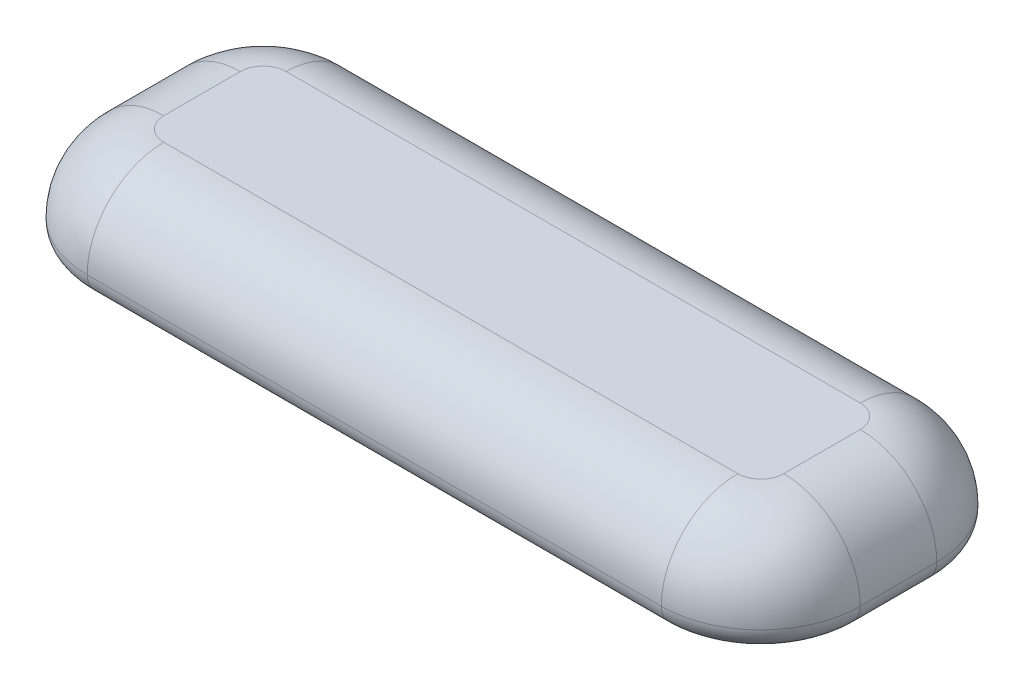
SolidWorks part; units mm, degrees
ref_plane "前视基准面" through (0, 0, 0) normal (0, 0, 1) x (1, 0, 0)
ref_plane "上视基准面" through (0, 0, 0) normal (0, 1, 0) x (1, 0, 0)
ref_plane "右视基准面" through (0, 0, 0) normal (1, 0, 0) x (0, 0, -1)
sketch "草图1" plane through (0, 0, 0) normal (0, 1, 0) x (1, 0, 0)
  line L1 (-37.5, 15) -> (37.5, 15)
  line L2 (-47.5, 5) -> (-47.5, -5)
  line L3 (-37.5, -15) -> (37.5, -15)
  line L4 (47.5, 5) -> (47.5, -5)
  line L5 (0, -15) -> (0, 15) construction
  line L6 (-47.5, 0) -> (47.5, 0) construction
  arc A0 (-47.5, -5) -> (-37.5, -15) centre (-37.5, -5) ccw
  arc A1 (-47.5, 5) -> (-37.5, 15) centre (-37.5, 5) cw
  arc A2 (37.5, 15) -> (47.5, 5) centre (37.5, 5) cw
  arc A3 (47.5, -5) -> (37.5, -15) centre (37.5, -5) cw
  point P0 (0, 0)
  point P8 (-47.5, 15)
  point P11 (47.5, 15)
  point P15 (47.5, -15)
  dimension "D3" = 10
  dimension "D1" = 95
  dimension "D2" = 30
extrude "凸台-拉伸1" add sketch "草图1" along normal blind 10
shell "抽壳2" thickness 3 removed face at (0, 0, 0) outward yes
fillet "圆角3" radius 10 8 edges at (46.6924, 13, -14.1924) (50.5, 13, 0) (46.6924, 13, 14.1924) (0, 13, 18) (-46.6924, 13, 14.1924) (-50.5, 13, 0) (-46.6924, 13, -14.1924) (0, 13, -18)
fillet "圆角4" radius 3 8 edges at (50.5, 0, 0) (46.6924, 0, 14.1924) (0, 0, 18) (-46.6924, 0, 14.1924) (-50.5, 0, 0) (-46.6924, 0, -14.1924) (0, 0, -18) (46.6924, 0, -14.1924)
ref_plane "基准面1" through (0, 10, 0) normal (0, -1, 0) x (-1, 0, 0)
sketch "草图2" plane through (0, 10, 0) normal (0, -1, 0) x (-1, 0, 0)
  line L0 (0, 0) -> (36.8, 0) construction
  line L1 (0, 0) -> (0, 6.5357) construction
  line L2 (34.725, 0.575) -> (38.875, 0.575)
  line L3 (34.725, 0.575) -> (34.725, -0.575)
  line L4 (34.725, -0.575) -> (38.875, -0.575)
  line L5 (38.875, 0.575) -> (38.875, -0.575)
  line L6 (36.8, -0.575) -> (36.8, 0.575) construction
  line L7 (34.725, 0) -> (38.875, 0) construction
  line L8 (36.225, 2.075) -> (37.375, 2.075)
  line L9 (36.225, 2.075) -> (36.225, -2.075)
  line L10 (36.225, -2.075) -> (37.375, -2.075)
  line L11 (37.375, 2.075) -> (37.375, -2.075)
  line L12 (36.8, -2.075) -> (36.8, 2.075) construction
  line L13 (36.225, 0) -> (37.375, 0) construction
  line L14 (-36.225, 0) -> (-37.375, 0) construction
  line L15 (-36.8, -2.075) -> (-36.8, 2.075) construction
  line L16 (-34.725, 0) -> (-38.875, 0) construction
  line L17 (-36.8, -0.575) -> (-36.8, 0.575) construction
  line L18 (-37.375, 2.075) -> (-37.375, -2.075)
  line L19 (-36.225, -2.075) -> (-37.375, -2.075)
  line L20 (-36.225, 2.075) -> (-36.225, -2.075)
  line L21 (-36.225, 2.075) -> (-37.375, 2.075)
  line L22 (-38.875, 0.575) -> (-38.875, -0.575)
  line L23 (-34.725, -0.575) -> (-38.875, -0.575)
  line L24 (-34.725, 0.575) -> (-34.725, -0.575)
  line L25 (-34.725, 0.575) -> (-38.875, 0.575)
  circle A0 centre (36.8, 0) radius 2.675
  circle A1 centre (-36.8, 0) radius 2.675
  dimension "D2" = 5.35
  dimension "D1" = 36.8
  dimension "D3" = 4.15
  dimension "D4" = 1.15
  dimension "D5" = 4.15
  dimension "D6" = 1.15
extrude "凸台-拉伸2" add sketch "草图2" along normal blind 8 contours A0 L8 L11 L2 L5 L4 L10 L9 L3 | A1 L25 L24 L23 L20 L19 L18 L22 L21 region at (-34.2007, 10, 0) region at (39.3993, 10, 0)
fillet "圆角7" radius 5 8 edges at (0, 10, 15) (44.5711, 10, 12.0711) (47.5, 10, 0) (44.5711, 10, -12.0711) (0, 10, -15) (-44.5711, 10, -12.0711) (-47.5, 10, 0) (-44.5711, 10, 12.0711)
chamfer "倒角1" distance 0.2 angle 45 12 edges at (36.8, 2, -2.075) (36.225, 2, -1.325) (35.475, 2, -0.575) (34.725, 2, 0) (35.475, 2, 0.575) (36.225, 2, 1.325) (36.8, 2, 2.075) (37.375, 2, 1.325) (38.125, 2, 0.575) (38.875, 2, 0) (38.125, 2, -0.575) (37.375, 2, -1.325)
chamfer "倒角2" distance 0.2 angle 45 12 edges at (-36.225, 2, -1.325) (-35.475, 2, -0.575) (-34.725, 2, 0) (-35.475, 2, 0.575) (-36.225, 2, 1.325) (-36.8, 2, 2.075) (-37.375, 2, 1.325) (-38.125, 2, 0.575) (-38.875, 2, 0) (-38.125, 2, -0.575) (-37.375, 2, -1.325) (-36.8, 2, -2.075)
fillet "圆角9" radius 5 1 edges at (36.8, 10, -2.675) second distance 5.5 conic rho 0.25 first distance on face at (36.8, 2, -2.675)
fillet "圆角10" radius 5 1 edges at (-36.8, 10, 2.675) second distance 5.5 conic rho 0.25 first distance on face at (-0.2815, 10, -1.25)
